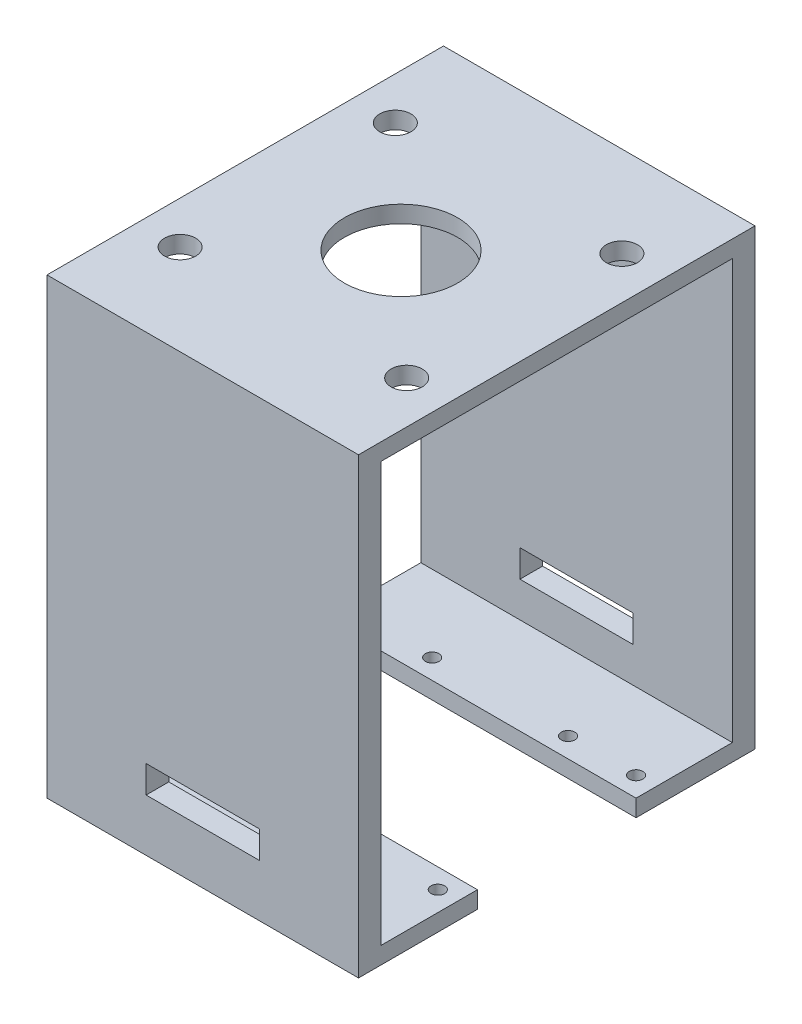
SolidWorks part; units mm, degrees
ref_plane "Front Plane" through (0, 0, 0) normal (0, 0, 1) x (1, 0, 0)
ref_plane "Top Plane" through (0, 0, 0) normal (0, 1, 0) x (1, 0, 0)
ref_plane "Right Plane" through (0, 0, 0) normal (1, 0, 0) x (0, 0, -1)
sketch "Sketch1" plane through (0, 0, 0) normal (0, 1, 0) x (1, 0, 0)
  line L0 (0, 0) -> (0, -14.43) construction
  line L1 (-37.5, 20) -> (37.5, 20)
  line L2 (-37.5, 20) -> (-37.5, -20)
  line L3 (-37.5, -20) -> (37.5, -20)
  line L4 (37.5, 20) -> (37.5, -20)
  line L5 (-37.5, 20) -> (37.5, -20) construction
  line L6 (-37.5, -20) -> (37.5, 20) construction
  line L7 (0, 0) -> (6.508, 0) construction
  line L8 (-5, 10) -> (5, 10)
  line L9 (-5, 10) -> (-5, -10)
  line L10 (-5, -10) -> (5, -10)
  line L11 (5, 10) -> (5, -10)
  line L12 (-5, 10) -> (5, -10) construction
  line L13 (-5, -10) -> (5, 10) construction
  circle A0 centre (-21, 0) radius 5
  circle A1 centre (-30, 8.25) radius 1.7
  circle A2 centre (-12, 8.25) radius 1.7
  circle A3 centre (-12, -8.25) radius 1.7
  circle A4 centre (-30, -8.25) radius 1.7
  circle A5 centre (12, 8.25) radius 1.7
  circle A6 centre (12, -8.25) radius 1.7
  circle A7 centre (21, 0) radius 5
  circle A8 centre (30, -8.25) radius 1.7
  circle A9 centre (30, 8.25) radius 1.7
  point P0 (0, 0)
  dimension "D3" = 10
  dimension "D4" = 16.5
  dimension "D5" = 16.5
  dimension "D6" = 18
  dimension "D9" = 10
  dimension "D11" = 20
  dimension "D13" = 7.5
  dimension "D17" = 3.4
  dimension "D19" = 11.75
  dimension "D20" = 11.75
  dimension "D1" = 75
  dimension "D2" = 40
  dimension "D10" = 10
  dimension "D7" = 2
  dimension "D8" = 2
extrude "Boss-Extrude1" add sketch "Sketch1" along normal blind 3
sketch "Sketch2" plane through (0, 3, 0) normal (0, 1, 0) x (1, 0, 0)
  line L0 (-37.5, 20) -> (-37.5, -20) construction
  line L1 (-33.5, 14) -> (33.5, 14)
  line L2 (-33.5, 14) -> (-33.5, -14)
  line L3 (-33.5, -14) -> (33.5, -14)
  line L4 (33.5, 14) -> (33.5, -14)
  line L5 (37.5, -20) -> (37.5, 20) construction
  line L6 (37.5, 20) -> (-37.5, 20) construction
  line L7 (-37.5, -20) -> (37.5, -20) construction
  dimension "D1" = 4
  dimension "D2" = 4
  dimension "D3" = 6
  dimension "D4" = 6
extrude "Cut-Extrude1" cut sketch "Sketch2" against normal through all both and the other way through all
sketch "Sketch3" plane through (0, 3, 0) normal (0, 1, 0) x (1, 0, 0)
  line L1 (37.5, 20) -> (-37.5, 20)
  line L2 (37.5, 20) -> (37.5, 35)
  line L3 (37.5, 35) -> (-37.5, 35)
  line L4 (-37.5, 20) -> (-37.5, 35)
  line L5 (-37.5, -20) -> (37.5, -20)
  line L6 (-37.5, -20) -> (-37.5, -35)
  line L7 (-37.5, -35) -> (37.5, -35)
  line L8 (37.5, -20) -> (37.5, -35)
  line L10 (-37.5, 20) -> (-33.5, 20)
  line L11 (-37.5, 20) -> (-37.5, -20)
  line L12 (-37.5, -20) -> (-33.5, -20)
  line L13 (-33.5, 20) -> (-33.5, -20)
  line L14 (37.5, 20) -> (33.5, 20)
  line L15 (37.5, 20) -> (37.5, -20)
  line L16 (37.5, -20) -> (33.5, -20)
  line L17 (33.5, 20) -> (33.5, -20)
  line M3 (-33.5, -14) -> (-33.5, 14)
  line M5 (33.5, 14) -> (33.5, -14)
  line M11 (37.5, -20) -> (37.5, 20)
  line M12 (37.5, 20) -> (-37.5, 20)
  line M13 (-37.5, 20) -> (-37.5, -20)
  line M14 (-37.5, -20) -> (37.5, -20)
  dimension "D1" = 15
  dimension "D2" = 15
extrude "Boss-Extrude3" add sketch "Sketch3" along normal blind 110 and the other way blind 3 contours L8 L5 L6 L7 M14 | L4 L1 L2 L3 M12 | L17 M12 M5 M14 M11 | L13 L1 M13 M14 M3 region at (35.5, 3, 0) region at (0, 3, -27.5) region at (0, 3, 27.5) region at (-35.5, 3, 0)
sketch "Sketch6" plane through (0, 3, 0) normal (0, 1, 0) x (1, 0, 0)
  line L0 (-37.5, -35) -> (37.5, -35) construction
  line L1 (-33.5, -20) -> (33.5, -20)
  line L2 (-33.5, -20) -> (-33.5, -31)
  line L3 (-33.5, -31) -> (33.5, -31)
  line L4 (33.5, -20) -> (33.5, -31)
  line L5 (33.5, 20) -> (-33.5, 20)
  line L6 (33.5, 20) -> (33.5, 31)
  line L7 (33.5, 31) -> (-33.5, 31)
  line L8 (-33.5, 20) -> (-33.5, 31)
  line L9 (37.5, 35) -> (-37.5, 35) construction
  dimension "D1" = 4
  dimension "D2" = 4
extrude "Cut-Extrude4" cut sketch "Sketch6" along normal through all
sketch "Sketch7" plane through (-37.5, 0, 0) normal (-1, 0, 0) x (0, 0, 1)
  line L0 (35, 0) -> (35, 113) construction
  line L1 (-35, 113) -> (35, 113)
  line L2 (-35, 113) -> (-35, 76)
  line L3 (-35, 76) -> (35, 76)
  line L4 (35, 113) -> (35, 76)
  dimension "D1" = 37
extrude "Boss-Extrude4" add sketch "Sketch7" along normal blind 45
ref_plane "Plane1" through (0, 0, 0) normal (1, 0, 0) x (0, 0, -1)
mirror "Mirror2" about plane through (0, 0, 0) normal (1, 0, 0) of "Boss-Extrude4"
sketch "Sketch8" plane through (0, 113, 0) normal (0, 1, 0) x (1, 0, 0)
  line L0 (-82.5, -35) -> (-82.5, 35) construction
  line L1 (-33.5, 31) -> (-78.5, 31)
  line L2 (-33.5, 31) -> (-33.5, -31)
  line L3 (-33.5, -31) -> (-78.5, -31)
  line L4 (-78.5, 31) -> (-78.5, -31)
  line L5 (33.5, -31) -> (78.5, -31)
  line L6 (33.5, -31) -> (33.5, 31)
  line L7 (33.5, 31) -> (78.5, 31)
  line L8 (78.5, -31) -> (78.5, 31)
  line L9 (82.5, -35) -> (82.5, 35) construction
  dimension "D1" = 4
  dimension "D2" = 4
extrude "Cut-Extrude6" cut sketch "Sketch8" against normal blind 29
sketch "Sketch9" plane through (-82.5, 0, 0) normal (-1, 0, 0) x (0, 0, 1)
  line L18 (-31, 84) -> (31, 84) construction
  line L19 (-19, 84) -> (19, 84)
  line L20 (-19, 84) -> (-19, 112.5)
  line L21 (-19, 112.5) -> (19, 112.5)
  line L22 (19, 84) -> (19, 112.5)
  line L25 (-31, 84) -> (-31, 113) construction
  dimension "D1" = 38
  dimension "D2" = 12
  dimension "D3" = 28.5
sketch "Sketch11" plane through (0, 0, 35) normal (0, 0, 1) x (1, 0, 0)
  line L0 (82.5, 76) -> (82.5, 113) construction
  line L1 (-82.5, 76) -> (-37.5, 76)
  line L2 (-82.5, 76) -> (-82.5, 80)
  line L3 (-82.5, 80) -> (-37.5, 80)
  line L4 (-37.5, 76) -> (-37.5, 80)
  line L5 (37.5, 76) -> (82.5, 76)
  line L6 (37.5, 76) -> (37.5, 80)
  line L7 (37.5, 80) -> (82.5, 80)
  line L8 (82.5, 76) -> (82.5, 80)
  line L11 (-78.5, 84) -> (-33.5, 84) construction
  line L12 (33.5, 84) -> (78.5, 84) construction
  dimension "D1" = 4
  dimension "D2" = 4
extrude "Cut-Extrude9" cut sketch "Sketch11" against normal through all
extrude "Cut-Extrude10" cut sketch "Sketch9" against normal through all
sketch "Sketch13" plane through (0, 84, 0) normal (0, 1, 0) x (1, 0, 0)
  line L0 (-78.5, 31) -> (-78.5, -31) construction
  line L1 (-57, 19) -> (-52, 19)
  line L2 (-57, 19) -> (-57, -19)
  line L3 (-57, -19) -> (-52, -19)
  line L4 (-52, 19) -> (-52, -19)
  line L7 (78.5, 31) -> (-78.5, 31) construction
  line L13 (-57, -19) -> (-57, 19)
  line L17 (-82.5, -19) -> (-107.5, -19)
  line L18 (-82.5, -19) -> (-82.5, 19)
  line L19 (-82.5, 19) -> (-107.5, 19)
  line L20 (-107.5, -19) -> (-107.5, 19)
  line L21 (-107.5, 19) -> (-61, 19)
  line L22 (-107.5, 19) -> (-107.5, -19)
  line L23 (-107.5, -19) -> (-61, -19)
  line L24 (-61, 19) -> (-61, -19)
  dimension "D1" = 21.5
  dimension "D2" = 5
  dimension "D3" = 38
  dimension "D4" = 12
  dimension "D5" = 25
  dimension "D6" = 46.5
extrude "Boss-Extrude5" add sketch "Sketch13" along normal blind 32 contours L4 L1 L2 L3 region at (-54.5, 84, 0)
sketch "Sketch14" plane through (-57, 0, 0) normal (-1, 0, 0) x (0, 0, 1)
  line L0 (-19, 116) -> (-19, 84) construction
  line L4 (19, 112.5) -> (-19, 112.5) construction
  circle A0 centre (0, 98.25) radius 5
  circle A1 centre (-9, 106.5) radius 1.7
  circle A2 centre (9, 106.5) radius 1.7
  circle A3 centre (9, 90) radius 1.7
  circle A4 centre (-9, 90) radius 1.7
  dimension "D1" = 19
  dimension "D2" = 9
  dimension "D3" = 10
  dimension "D6" = 3.4
  dimension "D7" = 14.25
  dimension "D8" = 16.5
  dimension "D9" = 18
  dimension "D10" = 8.25
  dimension "D4" = 2
  dimension "D5" = 2
extrude "Cut-Extrude11" cut sketch "Sketch14" against normal blind 32
mirror "Mirror4" about plane through (0, 0, 0) normal (1, 0, 0) of "Boss-Extrude5", "Cut-Extrude11"
sketch "Sketch15" plane through (0, 113, 0) normal (0, 1, 0) x (1, 0, 0)
  line L1 (-82.5, 35) -> (82.5, 35)
  line L2 (-82.5, 35) -> (-82.5, -35)
  line L3 (-82.5, -35) -> (82.5, -35)
  line L4 (82.5, 35) -> (82.5, -35)
  line L5 (-78.5, 31) -> (78.5, 31)
  line L6 (-78.5, 31) -> (-78.5, -31)
  line L7 (-78.5, -31) -> (78.5, -31)
  line L8 (78.5, 31) -> (78.5, -31)
extrude "Boss-Extrude6" add sketch "Sketch15" along normal blind 3
sketch "Sketch16" plane through (0, 0, 35) normal (0, 0, 1) x (1, 0, 0)
  line L1 (-10, 14.0464) -> (10, 14.0464)
  line L2 (-10, 14.0464) -> (-10, 9.2258)
  line L3 (-10, 9.2258) -> (10, 9.2258)
  line L4 (10, 14.0464) -> (10, 9.2258)
  line L5 (-37.5, 0) -> (-37.5, 80) construction
  dimension "D1" = 20
  dimension "D2" = 27.5
extrude "Cut-Extrude12" cut sketch "Sketch16" against normal through all
sketch "Sketch18" plane through (0, 0, 35) normal (0, 0, 1) x (1, 0, 0)
  line L0 (57, 116) -> (57, 84) construction
  line L2 (33.5, 84) -> (78.5, 84) construction
  circle A0 centre (67.75, 100) radius 5
  dimension "D1" = 10.75
  dimension "D2" = 16
  dimension "D3" = 10
extrude "Cut-Extrude14" cut sketch "Sketch18" against normal through all
mirror "Mirror5" about plane through (0, 0, 0) normal (1, 0, 0) of "Cut-Extrude14"
mirror "Mirror6" about plane through (0, 116, 0) normal (0, 1, 0) of "Mirror4"
sketch "Sketch19" plane through (82.5, 0, 0) normal (1, 0, 0) x (0, 0, -1)
  line L0 (19, 148) -> (19, 84) construction
  line L1 (-19, 112.5) -> (19, 112.5)
  line L2 (-19, 112.5) -> (-19, 116)
  line L3 (-19, 116) -> (19, 116)
  line L4 (19, 112.5) -> (19, 116)
extrude "Cut-Extrude15" cut sketch "Sketch19" against normal blind 10
mirror "Mirror7" about plane through (0, 0, 0) normal (1, 0, 0) of "Cut-Extrude15"
sketch "Sketch20" plane through (0, 3, 0) normal (0, 1, 0) x (1, 0, 0)
  line L0 (33.5, 31) -> (-33.5, 31) construction
  line L1 (-5, -10) -> (5, -10)
  line L2 (-5, -10) -> (-5, 10)
  line L3 (-5, 10) -> (5, 10)
  line L4 (5, -10) -> (5, 10)
  line L5 (-5, -10) -> (5, 10) construction
  line L6 (-5, 10) -> (5, -10) construction
  line L7 (0, 0) -> (0, 17.5) construction
  line L8 (-37.5, 20) -> (37.5, 20)
  line L9 (-37.5, 20) -> (-37.5, -20)
  line L10 (-37.5, -20) -> (37.5, -20)
  line L11 (37.5, 20) -> (37.5, -20)
  line L12 (-37.5, 20) -> (37.5, -20) construction
  line L13 (-37.5, -20) -> (37.5, 20) construction
  line L14 (0, -34.1) -> (0, 34.1) construction
  circle A1 centre (-12, 17.5) radius 1.2
  circle A2 centre (-12, -17.5) radius 1.2
  circle A3 centre (-24, -17.5) radius 1.2
  circle A4 centre (-24, 17.5) radius 1.2
  circle A5 centre (12, -17.5) radius 1.2
  circle A6 centre (24, -17.5) radius 1.2
  circle A7 centre (12, 17.5) radius 1.2
  circle A8 centre (24, 17.5) radius 1.2
  point P2 (0, 0)
  point P10 (0, 0)
  dimension "D1" = 7
  dimension "D2" = 10
  dimension "D4" = 2.5
  dimension "D7" = 35
  dimension "D8" = 7
  dimension "D9" = 2.4
  dimension "D11" = 12
  dimension "D3" = 21
  dimension "D5" = 75
  dimension "D6" = 40
  dimension "D10" = 2
extrude "Cut-Extrude16" cut sketch "Sketch20" against normal blind 10 contours A4 | A1 | A7 | A3 | A2 | A8 | A5 | A6 region at (-12, 3, -17.5) region at (-12, 3, 17.5) region at (-24, 3, 17.5) region at (-24, 3, -17.5) region at (12, 3, 17.5) region at (24, 3, 17.5) region at (12, 3, -17.5) region at (24, 3, -17.5)
sketch "Sketch21" plane through (0, 0, 35) normal (0, 0, 1) x (1, 0, 0)
  line L0 (0, -34.1) -> (0, 34.1) construction
  line L1 (37.5, 0) -> (27.5, 0)
  line L2 (37.5, 0) -> (37.5, 80)
  line L3 (37.5, 80) -> (27.5, 80)
  line L4 (27.5, 0) -> (27.5, 80)
  line L5 (-27.5, 0) -> (-27.5, 80)
  line L6 (-37.5, 80) -> (-27.5, 80)
  line L7 (-37.5, 0) -> (-37.5, 80)
  line L8 (-37.5, 0) -> (-27.5, 0)
  dimension "D1" = 10
  dimension "D2" = 80
extrude "Cut-Extrude17" cut sketch "Sketch21" against normal through all
sketch "Sketch22" plane through (0, 0, 35) normal (0, 0, 1) x (1, 0, 0)
  line L1 (82.5, 80) -> (-90.2391, 80)
  line L2 (82.5, 80) -> (82.5, 155.8432)
  line L3 (82.5, 155.8432) -> (-90.2391, 155.8432)
  line L4 (-90.2391, 80) -> (-90.2391, 155.8432)
extrude "Cut-Extrude18" cut sketch "Sketch22" against normal through all
sketch "Sketch23" plane through (0, 80, 0) normal (0, 1, 0) x (1, 0, 0)
  line L5 (-27.5, 35) -> (27.5, 35)
  line L6 (-27.5, 35) -> (-27.5, -35)
  line L7 (-27.5, -35) -> (27.5, -35)
  line L8 (27.5, 35) -> (27.5, -35)
extrude "Boss-Extrude7" add sketch "Sketch23" against normal blind 3
sketch "Sketch24" plane through (0, 80, 0) normal (0, 1, 0) x (1, 0, 0)
  line L0 (-27.5, 35) -> (27.5, 35) construction
  line L1 (-27.5, 35) -> (-27.5, -35) construction
  line L2 (0, -55) -> (0, 55) construction
  circle A0 centre (0, 0) radius 10
  circle A1 centre (-20, 19) radius 2.75
  circle A2 centre (-20, -19) radius 2.75
  circle A3 centre (20, -19) radius 2.75
  circle A4 centre (20, 19) radius 2.75
  point P0 (0, 0)
  dimension "D2" = 35
  dimension "D1" = 19
  dimension "D3" = 27.5
  dimension "D4" = 20
  dimension "D5" = 5.5
  dimension "D6" = 5.5
  dimension "D7" = 38
  dimension "D8" = 20
extrude "Cut-Extrude19" cut sketch "Sketch24" against normal blind 3
